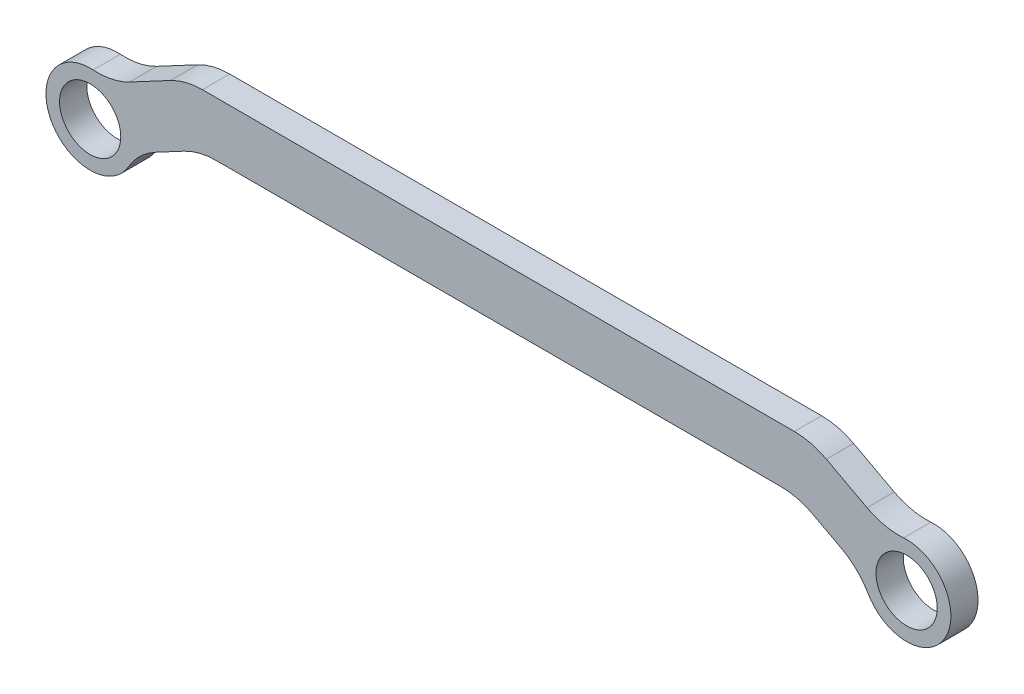
SolidWorks part; units mm, degrees
ref_plane "Front Plane" through (0, 0, 0) normal (0, 0, 1) x (1, 0, 0)
ref_plane "Top Plane" through (0, 0, 0) normal (0, 1, 0) x (1, 0, 0)
ref_plane "Right Plane" through (0, 0, 0) normal (1, 0, 0) x (0, 0, -1)
sketch "Sketch1" plane through (0, 0, 0) normal (0, 0, 1) x (1, 0, 0)
  line L0 (0, 0) -> (120, 0) construction
  line L1 (0, 0) -> (15, 8) construction
  line L3 (15, 8) -> (105, 8) construction
  line L5 (105, 8) -> (120, 0) construction
  line L6 (6.4031, -1.1184) -> (16, 4)
  line L7 (16, 4) -> (104, 4)
  line L8 (104, 4) -> (113.5969, -1.1184)
  line L9 (2.6384, 5.9405) -> (14, 12)
  line L10 (14, 12) -> (106, 12)
  line L11 (106, 12) -> (117.3616, 5.9405)
  line L12 (-1.8824, 3.5294) -> (14, 12) construction
  line L13 (1.8824, -3.5294) -> (16, 4) construction
  line L15 (106, 12) -> (121.8824, 3.5294) construction
  line L17 (104, 4) -> (118.1176, -3.5294) construction
  circle A0 centre (0, 0) radius 4.5
  circle A1 centre (0, 0) radius 6.5
  circle A2 centre (120, 0) radius 4.5
  circle A3 centre (120, 0) radius 6.5
  dimension "D1" = 9
  dimension "D2" = 13
  dimension "D4" = 9
  dimension "D5" = 13
  dimension "D3" = 120
  dimension "D6" = 8
  dimension "D7" = 90
  dimension "D8" = 4
  dimension "D9" = 4
extrude "Boss-Extrude1" add sketch "Sketch1" along normal blind 4 contours A3 L11 L10 L9 A1 L6 L7 L8 | A1 A0 | A3 A2 region at (60, 7.5424, 0) region at (-5.5731, -2.9723, 0) region at (114.4269, 2.9723, 0)
fillet "Fillet1" radius 10 8 edges at (113.5969, -1.1184, 2) (117.3616, 5.9405, 2) (104, 4, 2) (106, 12, 2) (16, 4, 2) (14, 12, 2) (6.4031, -1.1184, 2) (2.6384, 5.9405, 2)
